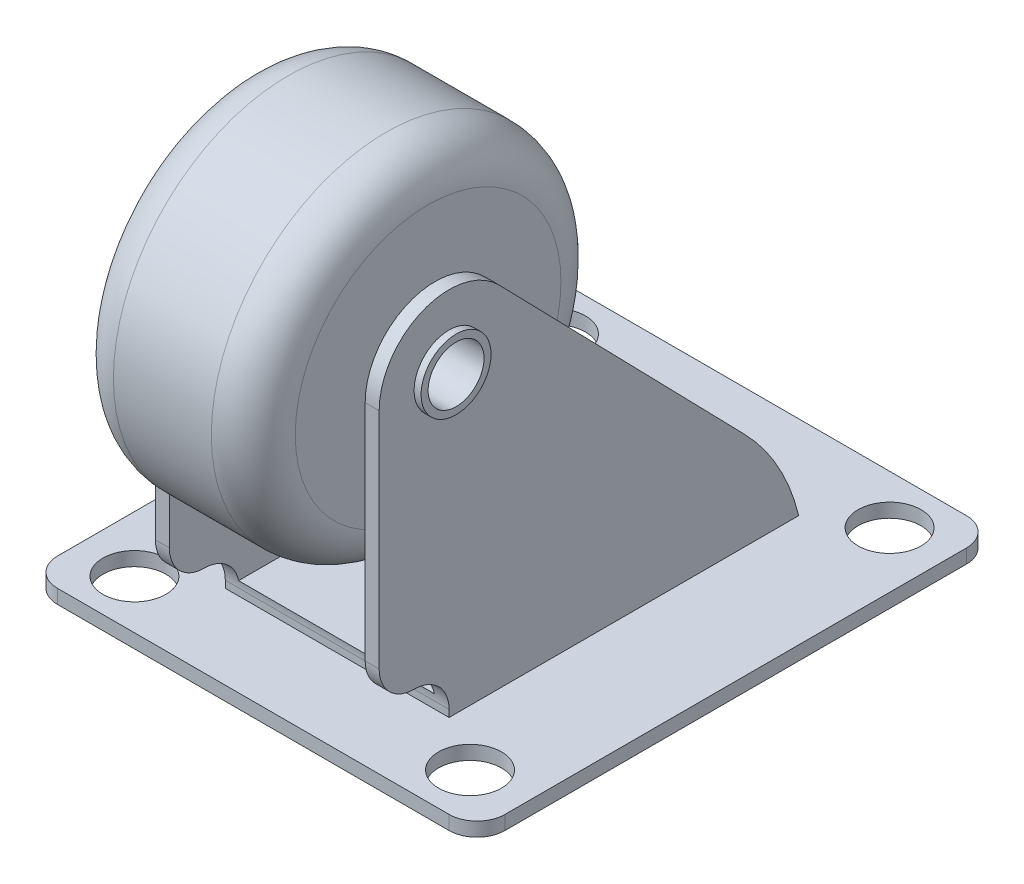
SolidWorks part; units mm, degrees
material "Aço carbono simples"
ref_plane "Plano frontal" through (0, 0, 0) normal (0, 0, 1) x (1, 0, 0)
ref_plane "Plano superior" through (0, 0, 0) normal (0, 1, 0) x (1, 0, 0)
ref_plane "Plano direito" through (0, 0, 0) normal (1, 0, 0) x (0, 0, -1)
sketch "Esboço1" plane through (0, 0, 0) normal (0, 1, 0) x (1, 0, 0)
  line L0 (4, 33.5) -> (28, 33.5) construction
  line L1 (2, 0) -> (30, 0)
  line L2 (0, 2) -> (0, 35)
  line L3 (2, 37) -> (30, 37)
  line L4 (32, 2) -> (32, 35)
  line L5 (28, 33.5) -> (28, 3.5) construction
  line L6 (28, 3.5) -> (4, 3.5) construction
  line L7 (4, 3.5) -> (4, 33.5) construction
  line L8 (4, 33.5) -> (0, 33.5) construction
  line L9 (28, 33.5) -> (32, 33.5) construction
  line L10 (4, 33.5) -> (4, 37) construction
  line L11 (4, 3.5) -> (4, 0) construction
  circle A0 centre (4, 33.5) radius 2.25
  circle A1 centre (28, 33.5) radius 2.25
  circle A2 centre (4, 3.5) radius 2.25
  circle A3 centre (28, 3.5) radius 2.25
  arc A4 (2, 0) -> (0, 2) centre (2, 2) cw
  arc A5 (30, 0) -> (32, 2) centre (30, 2) ccw
  arc A6 (30, 37) -> (32, 35) centre (30, 35) cw
  arc A7 (0, 35) -> (2, 37) centre (2, 35) cw
  point P19 (0, 0)
  point P22 (32, 0)
  point P25 (32, 37)
  dimension "D5" = 4.5
  dimension "D6" = 2
  dimension "D1" = 37
  dimension "D2" = 32
  dimension "D3" = 30
  dimension "D4" = 24
extrude "Ressalto-extrusão1" add sketch "Esboço1" along normal blind 1
ref_plane "Plano1" through (16, 0, 0) normal (1, 0, 0) x (0, 0, -1)
sketch "Esboço2" plane through (16, 0, 0) normal (1, 0, 0) x (0, 0, -1)
  line L0 (18.5, -999) -> (18.5, 49001) construction
  line L1 (2, 1) -> (35, 1) construction
  line L2 (-1001.1128, 35) -> (48998.8872, 35) construction
  line L3 (2, 0) -> (35, 0) construction
  line L4 (1, 22.5) -> (1, 4)
  line L5 (6, 1) -> (31, 1)
  line L6 (6, 1) -> (6, 4)
  line L8 (31, 1) -> (31, 4)
  line L9 (9.5817, 25.9888) -> (31, 4)
  line L10 (1, 4) -> (6, 4)
  circle A1 centre (6, 22.5) radius 2.5
  arc A2 (9.5817, 25.9888) -> (1, 22.5) centre (6, 22.5) ccw
  point P5 (18.5, 1)
  point P15 (0, 0)
  point P20 (0, 0)
  point P22 (3.7748, 1)
  point P23 (18.5, 1)
  dimension "D1" = 22.5
  dimension "D3" = 30
  dimension "D4" = 5
  dimension "D5" = 10
  dimension "D2" = 35
  dimension "D6" = 3
  dimension "D7" = 25
extrude "Ressalto-extrusão2" add sketch "Esboço2" along normal mid plane 16
sketch "Esboço3" plane through (0, 0, -1) normal (0, 0, 1) x (1, 0, 0)
  line L0 (24, 27.5) -> (8, 27.5) construction
  line L1 (9, 27.5) -> (23, 27.5)
  line L2 (9, 27.5) -> (9, 2)
  line L3 (9, 2) -> (23, 2)
  line L4 (23, 27.5) -> (23, 2)
  line L5 (24, 22.5) -> (24, 27.5) construction
  line L6 (8, 27.5) -> (8, 22.5) construction
  line L7 (2, 1) -> (30, 1) construction
  dimension "D1" = 1
  dimension "D2" = 1
  dimension "D3" = 1
extrude "Corte-extrusão1" cut sketch "Esboço3" against normal through all
sketch "Esboço5" plane through (16, 0, 0) normal (1, 0, 0) x (0, 0, -1)
  circle A0 centre (6, 22.5) radius 12.5
  circle A1 centre (6, 22.5) radius 2.5
  dimension "D1" = 25
  dimension "D2" = 5
extrude "Ressalto-extrusão3" add sketch "Esboço5" along normal mid plane 13 separate body
fillet "Filete1" radius 3 2 edges at (9.5, 22.5, -18.5) (22.5, 22.5, -18.5)
sketch "Esboço6" plane through (16, 0, 0) normal (1, 0, 0) x (0, 0, -1)
  circle A0 centre (6, 22.5) radius 2.5
  circle A1 centre (6, 22.5) radius 2
  circle A2 centre (6, 22.5) radius 2.5 construction
  dimension "D1" = 4
extrude "Ressalto-extrusão4" add sketch "Esboço6" along normal mid plane 17
fillet "Filete2" radius 2.5 3 edges at (23.5, 4, -6) (8.5, 4, -1) (23.5, 4, -1)
fillet "Filete3" radius 15 1 edges at (8.5, 4, -31)
